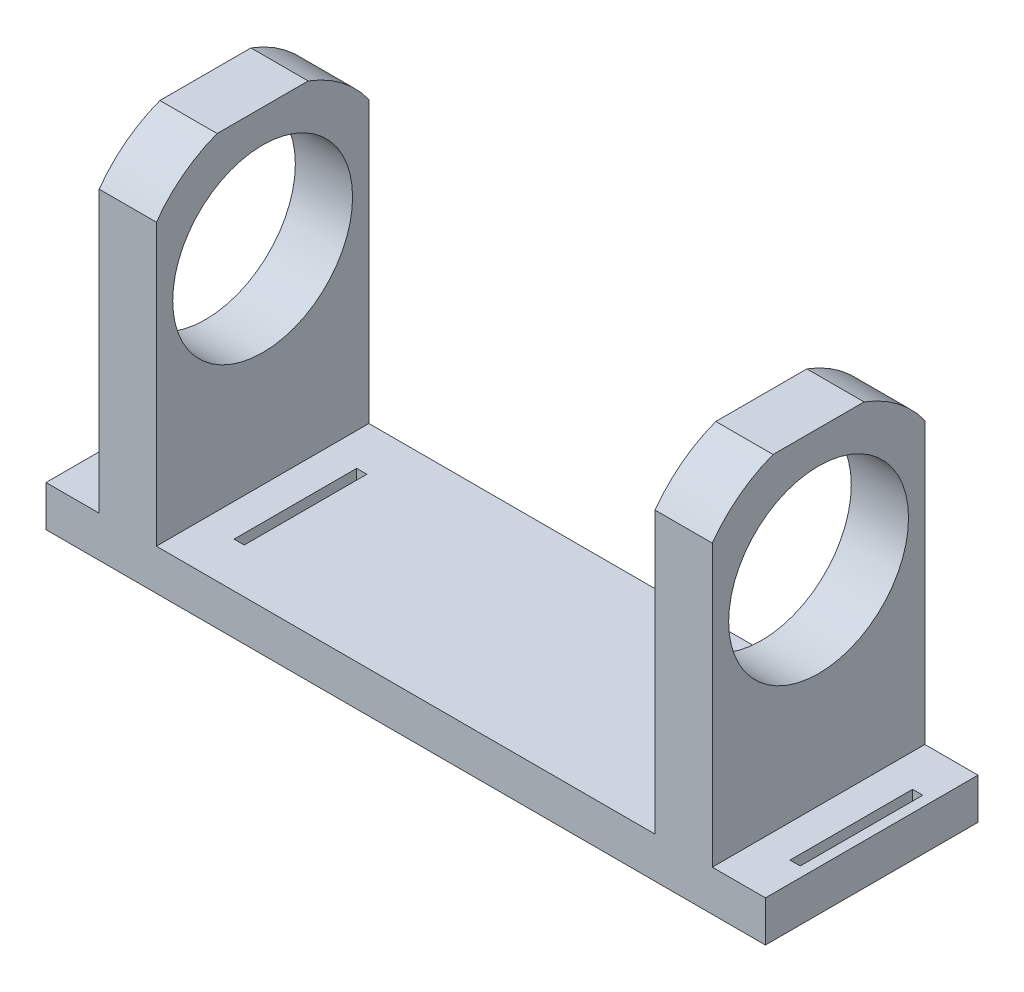
SolidWorks part; units mm, degrees
ref_plane "Front Plane" through (0, 0, 0) normal (0, 0, 1) x (1, 0, 0)
ref_plane "Top Plane" through (0, 0, 0) normal (0, 1, 0) x (1, 0, 0)
ref_plane "Right Plane" through (0, 0, 0) normal (1, 0, 0) x (0, 0, -1)
sketch "Sketch1" plane through (0, 0, 0) normal (0, 1, 0) x (1, 0, 0)
  line L0 (0, 0) -> (20, 0)
  line L1 (0, 0) -> (0, 26)
  line L2 (0, 26) -> (20, 26)
  line L3 (20, 26) -> (20, 0)
  line L4 (0, 26) -> (1.6662, 26)
  line L5 (2.5, 20.5) -> (2.5, 5.5)
  line L6 (20, 26) -> (16.6758, 26)
  line L7 (17.5008, 20.5) -> (17.5008, 5.5)
  line L8 (0, 26) -> (0.8331, 26)
  line L9 (1.25, 20.5) -> (1.25, 5.5)
  line L10 (18.7508, 20.5) -> (18.7508, 5.5)
  line L12 (17.5008, 20.5) -> (18.7508, 20.5)
  line L13 (0, 13) -> (20, 13) construction
  line L14 (17.5008, 5.5) -> (18.7508, 5.5)
  line L16 (2.5, 20.5) -> (1.25, 20.5)
  line L18 (2.5, 5.5) -> (1.25, 5.5)
  line L19 (10, 26) -> (10, 0) construction
  line L28 (14.1758, 26) -> (10, 26)
  dimension "D1" = 20
  dimension "D2" = 26
  dimension "D3" = 15
  dimension "D4" = 7.5
  dimension "D5" = 15.0008
  dimension "D6" = 7.5
  dimension "D7" = 1.25
sketch "Sketch2" plane through (0, 0, 0) normal (0, 1, 0) x (1, 0, 0)
  line L0 (2.5, 20.5) -> (4.675, 20.5)
  line L1 (4.675, 20.5) -> (7.4624, 20.5)
  line L2 (7.4624, 20.5) -> (10.4624, 20.5)
  line L3 (13.4624, 20.5) -> (10.4624, 20.5)
  line L4 (13.4624, 20.5) -> (16.2609, 20.5)
extrude "Boss-Extrude5" add sketch "Sketch1" along normal blind 5
sketch "Sketch3" plane through (0, 5, 0) normal (0, 1, 0) x (1, 0, 0)
  line L0 (2.5, 20.5) -> (2.5, 5.5) construction
  line L5 (6.5, 0) -> (13.5, 0)
  line L6 (6.5, 0) -> (6.5, 26)
  line L7 (6.5, 26) -> (13.5, 26)
  line L8 (13.5, 0) -> (13.5, 26)
  line L9 (6.5, 0) -> (13.5, 26) construction
  line L10 (6.5, 26) -> (13.5, 0) construction
  line L11 (0, 26) -> (20, 26) construction
  point P0 (10, 13)
  dimension "D1" = 7.5
  dimension "D2" = 7
  dimension "D3" = 26
  dimension "D4" = 13
extrude "Boss-Extrude6" add sketch "Sketch3" along normal blind 40
sketch "Sketch5" plane through (13.5, 0, 0) normal (1, 0, 0) x (0, 0, -1)
  line L0 (7.4322, 45) -> (0, 45)
  line L1 (26, 5) -> (0, 5) construction
  line L2 (13, 45) -> (13, 5) construction
  line L3 (0, 45) -> (26, 45) construction
  line L4 (0, 5) -> (26, 5) construction
  line L8 (0, 5) -> (26, 5)
  line L9 (26, 5) -> (26, 45)
  line L10 (26, 45) -> (0, 45)
  line L11 (0, 45) -> (0, 5)
  line L13 (26, 39.3274) -> (26, 45)
  line L14 (26, 45) -> (18.5678, 45)
  line L15 (0, 45) -> (0, 39.3274)
  circle A0 centre (13, 30) radius 11
  arc A1 (26, 39.3274) -> (18.5678, 45) centre (13, 30) ccw
  arc A2 (7.4322, 45) -> (0, 39.3274) centre (13, 30) ccw
  dimension "D1" = 32
  dimension "D2" = 22
  dimension "D3" = 25
  dimension "D4" = 0
extrude "Cut-Extrude1" cut sketch "Sketch5" against normal up to next
sketch "Sketch6" plane through (20, 0, 0) normal (1, 0, 0) x (0, 0, -1)
  line L1 (0, 0) -> (26, 0)
  line L2 (0, 0) -> (0, 5)
  line L3 (0, 5) -> (26, 5)
  line L4 (26, 0) -> (26, 5)
extrude "Boss-Extrude8" add sketch "Sketch6" along normal blind 24
mirror "Mirror5" about plane through (44, 0, 0) normal (-1, 0, 0) of "Cut-Extrude1", "Boss-Extrude8", "Boss-Extrude6", "Boss-Extrude5"
